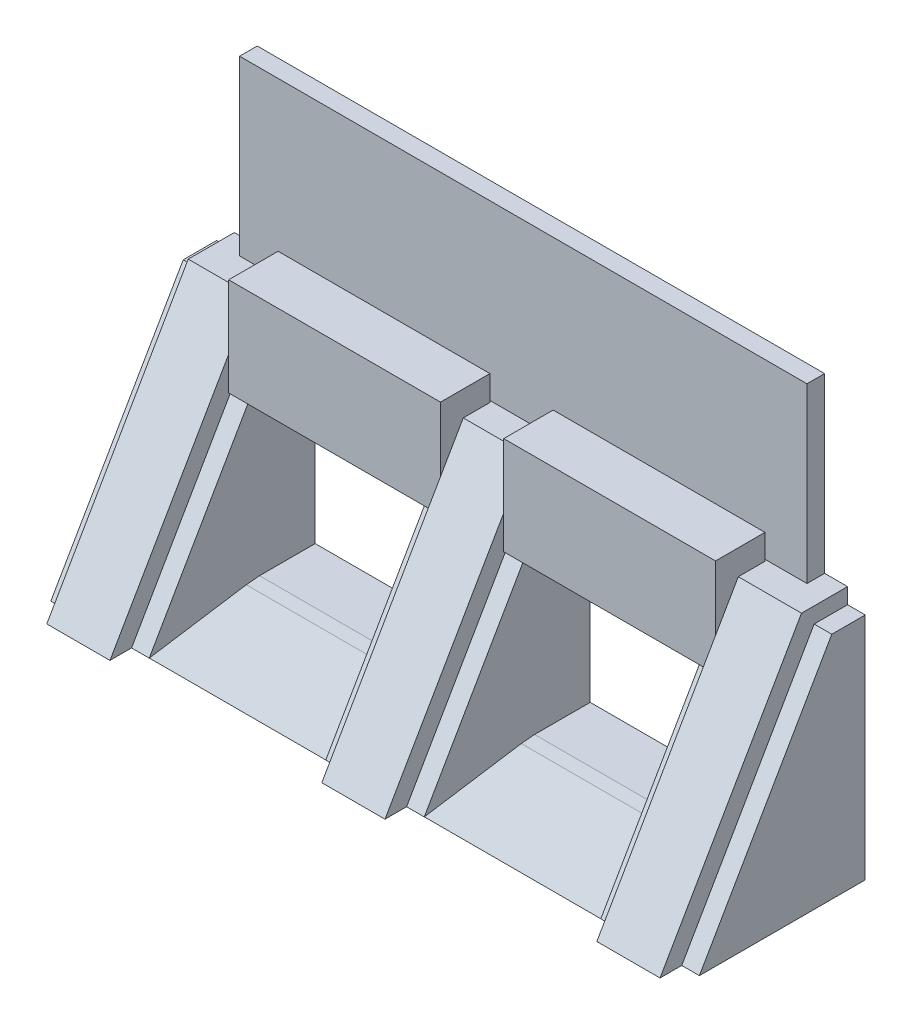
SolidWorks part; units mm, degrees
other "标注1"
sketch "草图12" plane through (1837, 2369, 956.2) normal (0.451, 0.5385, 0.7118) x (0.8923, -0.2537, -0.3735)
ref_plane "前视基准面" through (0, 0, 0) normal (0, 0, 1) x (1, 0, 0)
ref_plane "上视基准面" through (0, 0, 0) normal (0, 1, 0) x (1, 0, 0)
ref_plane "右视基准面" through (0, 0, 0) normal (1, 0, 0) x (0, 0, -1)
sketch "草图1" plane through (0, 0, 0) normal (0, 1, 0) x (1, 0, 0)
  line L0 (-746.0306, 0) -> (1002.7293, 0) construction
  line L1 (0, 910.4782) -> (0, -894.4345) construction
  line L3 (-1837, 956.2) -> (1837, 956.2)
  line L4 (-1837, 956.2) -> (-1837, -956.2)
  line L5 (-1837, -956.2) -> (1837, -956.2)
  line L6 (1837, 956.2) -> (1837, -956.2)
  line L7 (-1837, 956.2) -> (1837, -956.2) construction
  line L8 (-1837, -956.2) -> (1837, 956.2) construction
  point P1 (0, 0)
  dimension "D1" = 3674
  dimension "D2" = 1912.4
extrude "凸台-拉伸1" add sketch "草图1" along normal blind 1389
sketch "草图2" plane through (-1837, 0, 0) normal (-1, 0, 0) x (0, 0, 1)
  line L0 (-956.2, 0) -> (-956.2, 1389)
  line L1 (-956.2, 1389) -> (154.84, 1389)
  line L2 (-956.2, 1389) -> (956.2, 1389) construction
  line L3 (154.84, 1389) -> (956.2, 0)
  line L4 (956.2, 0) -> (-956.2, 0)
  line L5 (154.84, 1389) -> (956.2, 1389)
  line L6 (956.2, 1389) -> (956.2, 0)
  line M6 (956.2, 0) -> (956.2, 1389)
  line M7 (956.2, 1389) -> (-956.2, 1389)
  dimension "D1" = 1111.04
extrude "切除-拉伸1" cut sketch "草图2" against normal through all contours L3 M7 M6 region at (-1837, 926, 689.08)
sketch "草图3" plane through (1837, 0, 0) normal (1, 0, 0) x (0, 0, -1)
  line L0 (956.2, 1300) -> (-83.24, 1300)
  line L1 (956.2, 1389) -> (956.2, 0) construction
  line L2 (-83.24, 1300) -> (-833.253, 0)
  line L3 (-956.2, 0) -> (956.2, 0) construction
  line L4 (-833.253, 0) -> (956.2, 0)
  line L5 (956.2, 0) -> (956.2, 1300)
  line L6 (-154.84, 1389) -> (-956.2, 0) construction
  dimension "D1" = 1039.44
  dimension "D2" = 1300
ref_plane "基准面2" through (1837, 1389, 154.84) normal (0, 0, -1) x (-1, 0, 0)
sketch "草图5" plane through (1837, 0, 0) normal (1, 0, 0) x (0, 0, -1)
  line L0 (-154.84, 1389) -> (-956.2, 0)
  line L1 (-956.2, 0) -> (-833.253, 0)
  line L2 (956.2, 1300) -> (956.2, 1389)
  line L3 (956.2, 1389) -> (-154.84, 1389)
  line L8 (956.2, 1300) -> (-83.24, 1300)
  line L9 (-83.24, 1300) -> (-833.253, 0)
extrude "切除-拉伸3" cut sketch "草图5" against normal blind 100
extrude "切除-拉伸4" cut sketch "草图5<2>" along normal blind 100 from surface starting at face at (-1837, 694.5, -200.34)
sketch "草图5<2>" plane through (1837, 0, 0) normal (1, 0, 0) x (0, 0, -1) same geometry as "草图5"
sketch "草图6" plane through (0, 1389, 0) normal (0, 1, 0) x (1, 0, 0)
  line L0 (0, 1208.2195) -> (0, -1106.435) construction
  line L1 (1737, 956.2) -> (-1737, 956.2) construction
  line L2 (-1607, 956.2) -> (1607, 956.2)
  line L3 (-1607, 956.2) -> (-1607, 6.2)
  line L4 (-1607, 6.2) -> (1607, 6.2)
  line L5 (1607, 956.2) -> (1607, 6.2)
  dimension "D1" = 950
  dimension "D2" = 3214
extrude "凸台-拉伸2" add sketch "草图6" along normal blind 980
sketch "草图7" plane through (0, 413.897, 717.4091) normal (0, 0.4997, 0.8662) x (1, 0, 0)
  line L0 (1737, 1125.7486) -> (-1737, 1125.7486) construction
  line L1 (-1379, 1125.7486) -> (-1279, 1125.7486)
  line L2 (-1379, 1125.7486) -> (-1379, -477.8408)
  line L3 (-1379, -477.8408) -> (-1279, -477.8408)
  line L4 (-1279, 1125.7486) -> (-1279, -477.8408)
  line L5 (-1737, -477.8408) -> (1737, -477.8408) construction
  line L6 (-1737, -416.4006) -> (-1737, 1084.439) construction
  dimension "D1" = 358
  dimension "D2" = 100
extrude "切除-拉伸5" cut sketch "草图7" against normal blind 106
ref_plane "基准面3" through (0, 0, 956.2) normal (0, 0, 1) x (1, 0, 0)
sketch "草图8" plane through (0, 0, 956.2) normal (0, 0, 1) x (1, 0, 0)
  line L0 (-1279, 0) -> (1737, 0) construction
  line L1 (-1279, 1389) -> (-279, 1389)
  line L2 (-1279, 1389) -> (-1279, 0)
  line L3 (-1279, 0) -> (-279, 0)
  line L4 (-279, 1389) -> (-279, 0)
  dimension "D1" = 1000
extrude "切除-拉伸6" cut sketch "草图8" against normal through all
sketch "草图9" plane through (0, 413.897, 717.4091) normal (0, 0.4997, 0.8662) x (1, 0, 0)
  line L0 (-279, -477.8408) -> (1737, -477.8408) construction
  line L1 (-279, 1125.7486) -> (-179, 1125.7486)
  line L2 (-279, 1125.7486) -> (-279, -477.8408)
  line L3 (-279, -477.8408) -> (-179, -477.8408)
  line L4 (-179, 1125.7486) -> (-179, -477.8408)
  dimension "D1" = 100
extrude "切除-拉伸7" cut sketch "草图9" against normal blind 106
ref_plane "基准面4" through (-1379, 0, 956.2) normal (0, -0.8662, 0.4997) x (-1, 0, 0)
sketch "草图11" plane through (0, 413.897, 717.4091) normal (0, 0.4997, 0.8662) x (1, 0, 0)
  line L0 (1737, 1125.7486) -> (-179, 1125.7486) construction
  line L1 (179, 1125.7486) -> (279, 1125.7486)
  line L2 (179, 1125.7486) -> (179, -477.8408)
  line L3 (179, -477.8408) -> (279, -477.8408)
  line L4 (279, 1125.7486) -> (279, -477.8408)
  line L5 (-179, -477.8408) -> (1737, -477.8408) construction
  line L6 (-179, -477.8408) -> (-179, 1125.7486) construction
  dimension "D1" = 358
  dimension "D2" = 100
extrude "切除-拉伸8" cut sketch "草图11" against normal blind 106
sketch "草图14" plane through (0, 0, 956.2) normal (0, 0, 1) x (1, 0, 0)
  line L0 (279, 0) -> (1737, 0) construction
  line L1 (279, 1389) -> (1279, 1389)
  line L2 (279, 1389) -> (279, 0)
  line L3 (279, 0) -> (1279, 0)
  line L4 (1279, 1389) -> (1279, 0)
  dimension "D1" = 1000
extrude "切除-拉伸9" cut sketch "草图14" against normal through all
sketch "草图16" plane through (0, 413.897, 717.4091) normal (0, 0.4997, 0.8662) x (1, 0, 0)
  line L0 (1279, -477.8408) -> (1737, -477.8408) construction
  line L1 (1279, 1125.7486) -> (1379, 1125.7486)
  line L2 (1279, 1125.7486) -> (1279, -477.8408)
  line L3 (1279, -477.8408) -> (1379, -477.8408)
  line L4 (1379, 1125.7486) -> (1379, -477.8408)
  dimension "D1" = 100
extrude "切除-拉伸10" cut sketch "草图16" against normal blind 106
ref_plane "基准面5" through (0, 0, 3.8) normal (0, 0, 1) x (1, 0, 0)
sketch "草图18" plane through (0, 0, 3.8) normal (0, 0, 1) x (1, 0, 0)
  line L0 (-179, 0) -> (-179, 1336.0287) construction
  line L1 (-1379, 1531) -> (-179, 1531)
  line L2 (-1379, 1531) -> (-1379, 976)
  line L3 (-1379, 976) -> (-179, 976)
  line L4 (-179, 1531) -> (-179, 976)
  line L5 (-1379, 1389) -> (-1737, 1389) construction
  line L6 (1379, 0) -> (1379, 1389) construction
  line L7 (179, 1531) -> (1379, 1531)
  line L8 (179, 1531) -> (179, 976)
  line L9 (179, 976) -> (1379, 976)
  line L10 (1379, 1531) -> (1379, 976)
  line L11 (179, 1336.0287) -> (179, 0) construction
  dimension "D1" = 142
  dimension "D2" = 555
extrude "切除-拉伸11" cut sketch "草图18" along normal through all
extrude "凸台-拉伸3" add sketch "草图18<2>" along normal blind 280
sketch "草图18<2>" plane through (0, 0, 3.8) normal (0, 0, 1) x (1, 0, 0) same geometry as "草图18"
sketch "草图21" plane through (-1279, 0, 0) normal (1, 0, 0) x (0, 0, -1)
  line L0 (-833.253, 0) -> (-284.1184, 85.0382)
  line L1 (-284.1184, 85.0382) -> (-209.1184, 92.02)
  line L2 (-209.1184, 92.02) -> (956.2, 92.02)
  line L3 (956.2, 0) -> (956.2, 1300) construction
  line L4 (956.2, 92.02) -> (956.2, 0)
  line L5 (956.2, 0) -> (-833.253, 0)
  dimension "D1" = 92.02
  dimension "D2" = 555.68
  dimension "D3" = 75
extrude "凸台-拉伸4" add sketch "草图21" along normal up to next from surface starting at face at (-1279, 874.1429, -115.2056)
extrude "凸台-拉伸5" add sketch "草图21<2>" along normal up to next from surface starting at face at (279, 874.1429, -115.2056)
sketch "草图21<2>" plane through (-1279, 0, 0) normal (1, 0, 0) x (0, 0, -1) same geometry as "草图21"
sketch "草图23" plane through (0, 0, -956.2) normal (0, 0, -1) x (-1, 0, 0)
  line L1 (-1837, 0) -> (1837, 0)
  line L2 (-1837, 0) -> (-1837, 2369)
  line L3 (-1837, 2369) -> (1837, 2369)
  line L4 (1837, 0) -> (1837, 2369)
  line L6 (1837, 0) -> (1837, 1300) construction
  line L7 (1607, 2369) -> (-1607, 2369) construction
extrude "切除-拉伸12" cut sketch "草图23" against normal blind 850
